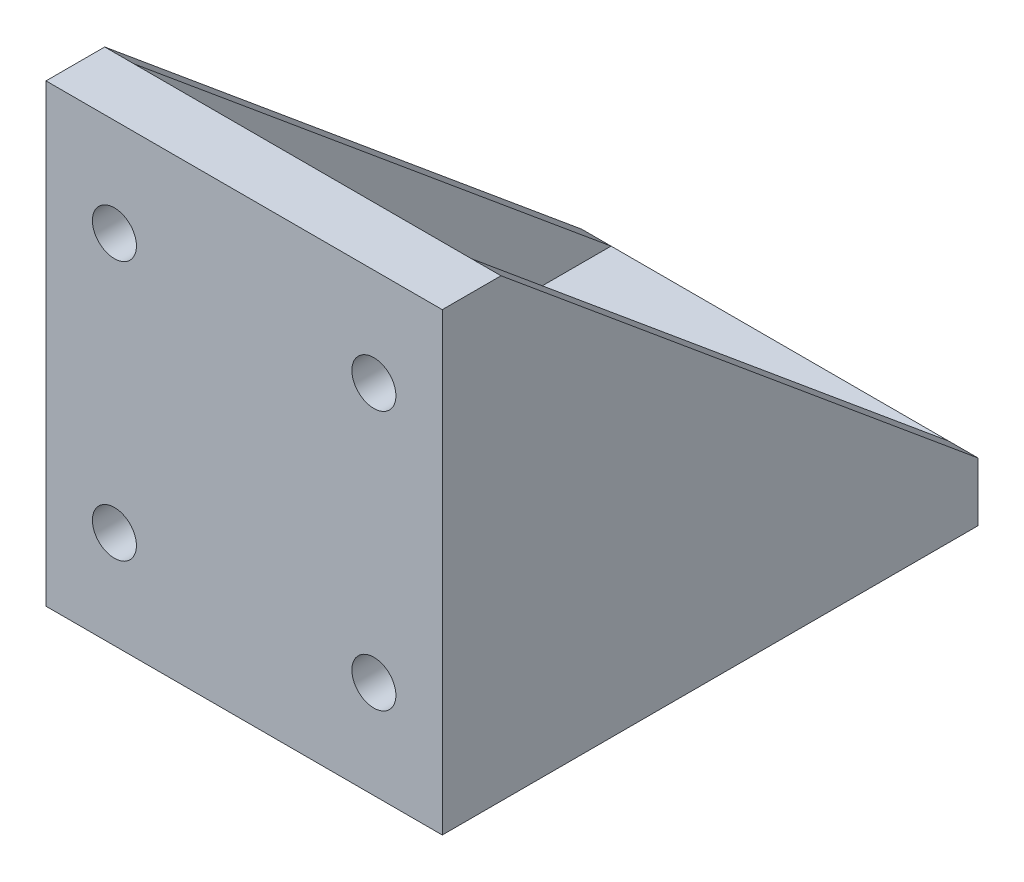
SolidWorks part; units mm, degrees
ref_plane "Front Plane" through (0, 0, 0) normal (0, 0, 1) x (1, 0, 0)
ref_plane "Top Plane" through (0, 0, 0) normal (0, 1, 0) x (1, 0, 0)
ref_plane "Right Plane" through (0, 0, 0) normal (1, 0, 0) x (0, 0, -1)
ref_plane "Plane1" through (0, 0, -35) normal (0, 0, 1) x (1, 0, 0)
sketch "Sketch1" plane through (0, 0, 0) normal (1, 0, 0) x (0, 0, -1)
  line L0 (0, 31) -> (0, -31)
  line L2 (73, -31) -> (73, -23)
  line L3 (73, -23) -> (8, 31)
  line L4 (8, 31) -> (0, 31)
  line L5 (73, -31) -> (0, -31)
  point P4 (0, 0)
  point P9 (36.5, -31)
  dimension "D1" = 62
  dimension "D2" = 8
  dimension "D3" = 73
extrude "Boss-Extrude1" add sketch "Sketch1" along normal blind 27 and the other way blind 27
sketch "Sketch4" plane through (0, 0, 0) normal (0, 0, 1) x (1, 0, 0)
  line L0 (-27, 31) -> (27, 31) construction
  line L1 (-23, 31) -> (23, 31)
  line L2 (-23, 31) -> (-23, -23)
  line L3 (-23, -23) -> (23, -23)
  line L4 (23, 31) -> (23, -23)
  line L6 (-27, 31) -> (-27, -31) construction
  line L7 (27, 31) -> (27, -31) construction
  line L8 (-27, -31) -> (27, -31) construction
  dimension "D1" = 8
  dimension "D2" = 4
  dimension "D3" = 4
extrude "Cut-Extrude1" cut sketch "Sketch4" against normal through all from offset 8 offset against normal yes
sketch "Sketch5" plane through (0, 0, 0) normal (0, 0, -1) x (-1, 0, 0)
  line L1 (0, 0) -> (0, 25) construction
  line L2 (0, 0) -> (17.6777, -17.6777) construction
  circle A0 centre (0, 0) radius 25 construction
  circle A1 centre (17.6777, 17.6777) radius 3
  circle A5 centre (17.6777, -17.6777) radius 3
  circle A6 centre (-17.6777, -17.6777) radius 3
  circle A7 centre (-17.6777, 17.6777) radius 3
  circle A8 centre (-17.6777, -17.6777) radius 5 construction
  point P14 (0, 0)
  dimension "D1" = 6
  dimension "D2" = 50
  dimension "D4" = 10
  dimension "D5" = 135
  dimension "D3" = 4
extrude "Cut-Extrude2" cut sketch "Sketch5" along normal through all
sketch "Sketch6" plane through (0, -31, -35) normal (0, 1, 0) x (1, 0, 0)
  line L0 (0, -69.1) -> (0, -0.9) construction
  line L7 (0, -21) -> (0, 24) construction
  line L9 (18, 1.5) -> (-18, 1.5) construction
  line L11 (-23, 38) -> (23, 38) construction
  circle A4 centre (0, -21) radius 2
  circle A5 centre (0, 24) radius 2
  circle A6 centre (18, 1.5) radius 2
  circle A7 centre (-18, 1.5) radius 2
  point P3 (0, 1.5)
  point P4 (0, 1.5)
  point P5 (0, 1.5)
  point P11 (0, 0)
  dimension "D1" = 36
  dimension "D2" = 45
  dimension "D3" = 14
  dimension "D5" = 4
extrude "Cut-Extrude4" cut sketch "Sketch6" along normal blind 10
